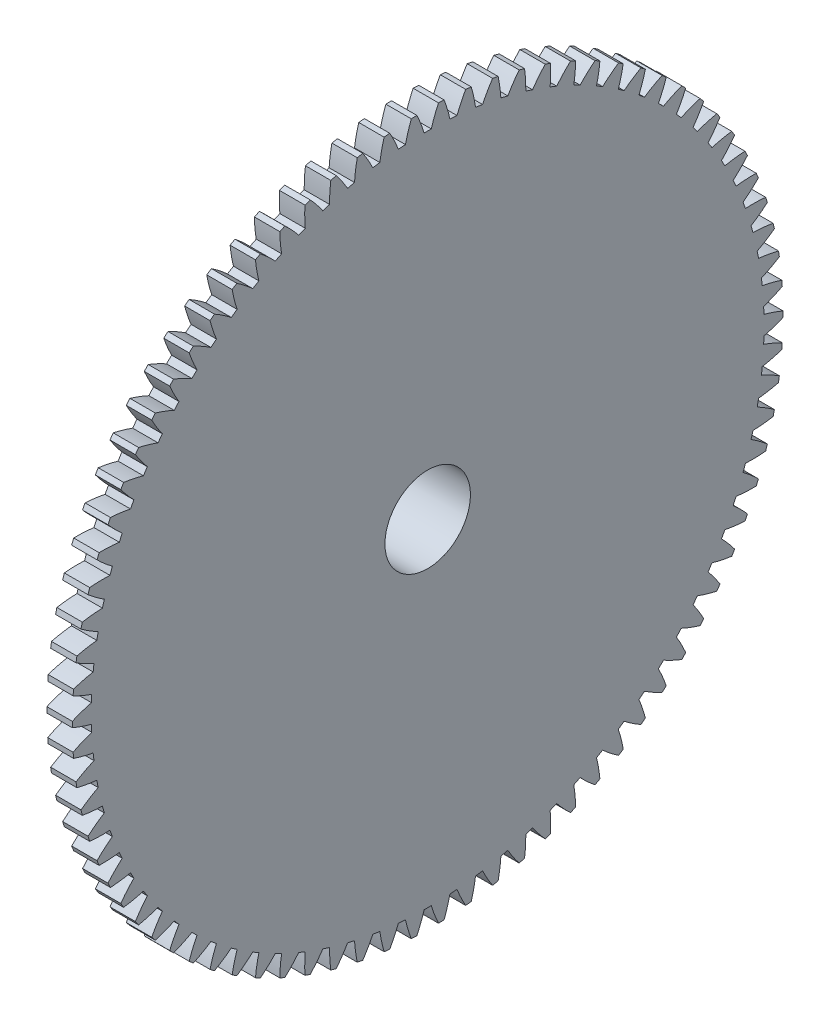
SolidWorks part; units mm, degrees
ref_plane "Plane1" through (0, 0, 0) normal (0, 0, 1) x (1, 0, 0)
ref_plane "Plane2" through (0, 0, 0) normal (0, 1, 0) x (1, 0, 0)
ref_plane "Plane3" through (0, 0, 0) normal (1, 0, 0) x (0, 0, -1)
sketch "HoldingSke" plane through (0, 0, 0) normal (0, 1, 0) x (1, 0, 0)
  line L0 (0, 0) -> (0.1392, -0.9903)
  line L1 (-15, 0) -> (100, 0) construction
  line L2 (0, 0) -> (-2.1039, 2.3779)
  line L3 (0, 0) -> (-11.863, 4.5341)
  line L4 (0, 0) -> (1.2019, 8.552)
  line L5 (0, 0) -> (-46.8476, -17.4728)
  line L6 (0, 0) -> (-2.4869, -1.6779)
  line L7 (-2.1039, 2.3779) -> (8.6586, 51.2059)
  line L8 (-76.2, 54.61) -> (-75.2, 54.61)
  line L9 (-71.009, 38.7566) -> (-53.1078, 45.2721)
  line L10 (-76.2, 71.12) -> (104.1128, 71.12)
  line L11 (0, 0) -> (-3, 0)
  line L12 (-76.2, 101.6) -> (-76.162, 101.6)
  line L13 (24.9733, 27.94) -> (52.9518, 28.4284)
  line L14 (24.9733, 27.94) -> (24.9743, 27.94)
  line L15 (24.9733, 27.94) -> (100.4006, 29.5858)
  line L16 (-63.627, -1) -> (-12.827, -1)
  circle A0 centre (0, 0) radius 3
  circle A1 centre (0, 0) radius 37.5
  circle A2 centre (0, 0) radius 37.5
  circle A3 centre (0, 0) radius 3
  dimension "MHD" = 75
  dimension "Hub_dia" = 75
  dimension "Bore" = 6
  dimension "MBD" = 6
  dimension "Num_teeth" = 82
  dimension "Pitch" = 1
  dimension "Overall_len" = 50
  dimension "Show_teeth" = 82
  dimension "Thickness" = 3
  dimension "OAL" = 50.0001
  dimension "T_dim" = 1
  dimension "Ap" = 20
  dimension "H" = 19.05
  dimension "Pitch_radius" = 180.3128
  dimension "Width" = 3
  dimension "Backlash" = 0.038
  dimension "Addendum_fac" = 1
  dimension "Dedendum_fac" = 1.25
  dimension "Clearance_fac" = 0.25
  dimension "Dedendum_add" = 0.001
  dimension "Module" = 1
sketch "BasProSke" plane through (0, 0, 0) normal (0, 1, 0) x (1, 0, 0)
  line L0 (-10, 0) -> (60, 0) construction
  line L1 (0, 0) -> (0, 42)
  line L2 (0, 0) -> (3, 0)
  line L3 (3, 0) -> (3, 42)
  line L4 (3, 42) -> (0, 42)
  dimension "Thickness" = 3
  dimension "Diameter" = 84
revolve "Base-Revolve" add sketch "BasProSke" angle 360 about L0
sketch "TooCutSke" plane through (0, 0, 0) normal (1, 0, 0) x (0, 0, -1)
  line L1 (0, 0) -> (0, 107) construction
  line L2 (0, 0) -> (-0.8518, 40.9911) construction
  line L3 (0, 0) -> (-3.1403, 81.9272) construction
  line L4 (-0.8518, 40.9911) -> (-1.5702, 40.9636) construction
  arc A0 (0.4198, 39.7468) -> (-0.4198, 39.7468) centre (0, 0) ccw
  arc A1 (1.2904, 42.0056) -> (-1.2904, 42.0056) centre (0, 0) ccw
  circle A2 centre (0, 0) radius 41 construction
  circle A3 centre (0, 0) radius 38.5274 construction
  arc A4 (-0.4198, 39.7468) -> (-1.2904, 42.0056) centre (-16.1163, 34.9947) ccw
  arc A5 (1.2904, 42.0056) -> (0.4198, 39.7468) centre (16.1163, 34.9947) ccw
  dimension "Root_dia" = 79.498
  dimension "Overcut_dia" = 84.0508
  dimension "Pitch_dia" = 82
  dimension "Base_dia" = 77.0548
  dimension "Flank_rad" = 16.4
  dimension "Half_ang" = 2.195
  dimension "Half_CT" = 0.7189
extrude "ToothCut" cut sketch "TooCutSke" along normal through all
fillet "Breaks" [suppressed] radius 0.02 tangent propagation no
fillet "RootFillets" [suppressed] radius 0.251
pattern_circular "TeethCuts" count 82 over 360 about axis through (-10, 0, 0) along (1, 0, 0) of "ToothCut", "RootFillets", "Breaks"
sketch "HubNeaOneSke" plane through (0, 0, 0) normal (-1, 0, 0) x (0, 0, 1)
  circle A0 centre (0, 0) radius 37.5
  dimension "Diameter" = 75
extrude "HubNearOne" [suppressed] add sketch "HubNeaOneSke" along normal blind 47.0001
sketch "HubNeaBotSke" plane through (0, 0, 0) normal (-1, 0, 0) x (0, 0, 1)
  circle A0 centre (0, 0) radius 37.5
  dimension "Diameter" = 75
extrude "HubNearBoth" [suppressed] add sketch "HubNeaBotSke" along normal blind 23.5
ref_plane "FarPln" through (3, 0, 0) normal (1, 0, 0) x (0, 0, -1)
sketch "HubFarSke" plane through (3, 0, 0) normal (1, 0, 0) x (0, 0, -1)
  circle A0 centre (0, 0) radius 37.5
  dimension "Diameter" = 75
extrude "HubFar" [suppressed] add sketch "HubFarSke" along normal blind 23.5
sketch "BorSke" plane through (0, 0, 0) normal (1, 0, 0) x (0, 0, -1)
  circle A0 centre (0, 0) radius 3
  dimension "Diameter" = 6
extrude "Bore" cut sketch "BorSke" along normal mid plane 100.0001
sketch "KeySke" plane through (0, 0, 0) normal (1, 0, 0) x (0, 0, -1)
  line L0 (-1, 0) -> (-1, 4)
  line L1 (-1, 4) -> (1, 4)
  line L2 (1, 4) -> (1, 0)
  line L3 (0, 0) -> (0, 34) construction
  line L4 (-1, 0) -> (1, 0)
  dimension "Offset" = 4
  dimension "Width" = 2
extrude "Keyway" [suppressed] cut sketch "KeySke" along normal mid plane 100.0001
pattern_circular "Keyway2" [suppressed] count 2 every 90 about axis through (-10, 0, 0) along (1, 0, 0) reverse direction yes
sketch "Sketch1" plane through (3, 0, 0) normal (1, 0, 0) x (0, 0, -1)
  circle A0 centre (0, 0) radius 3 construction
  circle A1 centre (0, 0) radius 3
extrude "Boss-Extrude1" add sketch "Sketch1" against normal up to surface (3 mm away) up to face at (0, 0, -3)
sketch "Sketch2" plane through (3, 0, 0) normal (1, 0, 0) x (0, 0, -1)
  line L0 (-1.8, 2.0125) -> (-1.8, -2.0125)
  line L1 (1.8, 2.0125) -> (1.8, -2.0125)
  line L2 (-1.8, 0) -> (1.8, 0) construction
  circle A0 centre (0, 0) radius 2.7
  point P9 (0, 0)
  dimension "D1" = 5.4
  dimension "D2" = 3.6
extrude "Cut-Extrude1" cut sketch "Sketch2" against normal up to surface (3 mm away) contours L0 L2 L1 A0 | L2 L0 A0 L1 region at (3, 1.25, 0) region at (3, -1.25, 0) up to face at (0, 0, 0)
sketch "Sketch3" plane through (3, 0, 0) normal (1, 0, 0) x (0, 0, -1)
  circle A0 centre (0, 0) radius 3
  dimension "D1" = 6
extrude "Cut-Extrude2" cut sketch "Sketch3" against normal up to surface (3 mm away) up to face at (0, 0, 0)
sketch "Sketch4" plane through (0, 0, 0) normal (-1, 0, 0) x (0, 0, 1)
  circle A0 centre (0, 0) radius 5.05
  dimension "D1" = 10.1
extrude "Cut-Extrude3" cut sketch "Sketch4" against normal through all
sketch "Sketch5" plane through (0, 0, 0) normal (-1, 0, 0) x (0, 0, 1)
  line L1 (6.2989, -3.5812) -> (6.2508, 3.6644)
  line L2 (6.2508, 3.6644) -> (-0.048, 7.2456)
  line L3 (-0.048, 7.2456) -> (-6.2989, 3.5812)
  line L4 (-6.2989, 3.5812) -> (-6.2508, -3.6644)
  line L5 (-6.2508, -3.6644) -> (0.048, -7.2456)
  line L6 (0.048, -7.2456) -> (6.2989, -3.5812)
  circle A0 centre (0, 0) radius 5.05 construction
  circle A1 centre (0, 0) radius 5.05
  circle A2 centre (0, 0) radius 6.275 construction
  dimension "D1" = 12.55
extrude "Boss-Extrude2" add sketch "Sketch5" along normal blind 12.85
sketch "Sketch6" plane through (0, 0, 0) normal (-1, 0, 0) x (0, 0, 1)
  line L12 (0.0557, -8.4003) -> (7.3027, -4.1519)
  line L13 (7.3027, -4.1519) -> (7.247, 4.2484)
  line L14 (7.247, 4.2484) -> (-0.0557, 8.4003)
  line L15 (-0.0557, 8.4003) -> (-7.3027, 4.1519)
  line L16 (-7.3027, 4.1519) -> (-7.247, -4.2484)
  line L17 (-7.247, -4.2484) -> (0.0557, -8.4003)
  line L18 (0.0557, -8.4003) -> (7.3027, -4.1519)
  line L19 (7.3027, -4.1519) -> (7.247, 4.2484)
  line L20 (7.247, 4.2484) -> (-0.0557, 8.4003)
  line L21 (-0.0557, 8.4003) -> (-7.3027, 4.1519)
  line L22 (-7.3027, 4.1519) -> (-7.247, -4.2484)
  line L23 (-7.247, -4.2484) -> (0.0557, -8.4003)
  dimension "D1" = 1
extrude "Boss-Extrude3" add sketch "Sketch6" along normal blind 5.05
sketch "Sketch7" plane through (-12.85, 0, 0) normal (-1, 0, 0) x (0, 0, 1)
  circle A0 centre (0, 0) radius 5.05 construction
  circle A1 centre (0, 0) radius 5.05
extrude "Cut-Extrude4" cut sketch "Sketch7" against normal up to surface (15.85 mm away) up to face at (3, 0, 5.05)
equation "' \"Module@HoldingSke\" = 6.35"
equation "' \"Num_teeth@HoldingSke\" = 12"
equation "' \"Ap@HoldingSke\" =  20"
equation "' \"Ap@HoldingSke\" = 20"
equation "' \"Width@HoldingSke\" = 0.5 * 25.4"
equation "' \"Hub_dia@HoldingSke\"= 1 * 25.4"
equation "' \"Hub_dia@HoldingSke\" = 1 * 25.4"
equation "' \"Overall_len@HoldingSke\" = 1.0 * 25.4"
equation "' \"Bore@HoldingSke\" = 0.75 * 25.4"
equation "' \"T_dim@HoldingSke\" = 0.1 * 25.4"
equation "' \"Width@KeySke\" = 0.25 * 25.4"
equation "' \"Show_teeth@HoldingSke\" = 13"
equation "' \"Backlash@HoldingSke\" = 0.009 * 25.4"
equation "' \"Addendum_fac@HoldingSke\" = 1.0"
equation "' \"Dedendum_fac@HoldingSke\" = 1.25"
equation "' \"Dedendum_add@HoldingSke\" = 0.00005 * 25.4"
equation "' \"Clearance_fac@HoldingSke\" = 0.25"
equation "\"Pitch@HoldingSke\" = 1 / \"Module@HoldingSke\""
equation "\"Overcut_dia@TooCutSke\" = (\"Num_teeth@HoldingSke\" + 2 * \"Addendum_fac@HoldingSke\") / \"Pitch@HoldingSke\" + 0.002 * 25.4"
equation "\"Pitch_dia@TooCutSke\" = \"Num_teeth@HoldingSke\" / \"Pitch@HoldingSke\""
equation "\"Base_dia@TooCutSke\" = \"Num_teeth@HoldingSke\" / \"Pitch@HoldingSke\" * cos((\"Ap@HoldingSke\"  * 3.14159265 / 180))"
equation "\"Root_dia@TooCutSke\" = (\"Num_teeth@HoldingSke\" + 2) / \"Pitch@HoldingSke\" - 2 * (\"Addendum_fac@HoldingSke\" + \"Dedendum_fac@HoldingSke\") / \"Pitch@HoldingSke\" - \"Dedendum_add@HoldingSke\" * 2"
equation "\"Half_ang@TooCutSke\" = 180 / \"Num_teeth@HoldingSke\""
equation "\"Half_CT@TooCutSke\" = \"Num_teeth@HoldingSke\" / \"Pitch@HoldingSke\" * sin((3.14159265 / 2 / \"Num_teeth@HoldingSke\")) / 2 - 7 * \"Backlash@HoldingSke\" / 4"
equation "\"Flank_rad@TooCutSke\" = \"Num_teeth@HoldingSke\" / \"Pitch@HoldingSke\" / 5"
equation "\"Radius@RootFillets\" = \"Clearance_fac@HoldingSke\" / \"Pitch@HoldingSke\" + \"Dedendum_add@HoldingSke\""
equation "\"Break_rad@Breaks\" = 0.02 / \"Pitch@HoldingSke\""
equation "\"Thickness@HoldingSke\" = \"Width@HoldingSke\""
equation "\"OAL@HoldingSke\" = \"Thickness@HoldingSke\""
equation "\"MHD@HoldingSke\" = (\"Num_teeth@HoldingSke\" + 2) / \"Pitch@HoldingSke\" - 2 * (\"Addendum_fac@HoldingSke\" + \"Dedendum_fac@HoldingSke\")  / \"Pitch@HoldingSke\" - \"Dedendum_add@HoldingSke\" * 2"
equation "\"MBD@HoldingSke\" = (\"Num_teeth@HoldingSke\" + 2) / \"Pitch@HoldingSke\" - 2 * (\"Addendum_fac@HoldingSke\" + \"Dedendum_fac@HoldingSke\")  / \"Pitch@HoldingSke\" - \"Dedendum_add@HoldingSke\" * 2 - 0.002 * 25.4"
equation "\"MHD@HoldingSke\" = ((sgn( \"MHD@HoldingSke\" - \"Hub_dia@HoldingSke\" )-1)*( \"MHD@HoldingSke\" - \"Hub_dia@HoldingSke\" ))/-2+ \"Hub_dia@HoldingSke\""
equation "\"MBD@HoldingSke\" = ((sgn( \"MBD@HoldingSke\" - \"Bore@HoldingSke\" )-1)*( \"MBD@HoldingSke\" - \"Bore@HoldingSke\" ))/-2+ \"Bore@HoldingSke\""
equation "\"OAL@HoldingSke\" = ((sgn( \"OAL@HoldingSke\" - \"Overall_len@HoldingSke\" )+1)*( \"OAL@HoldingSke\" - \"Overall_len@HoldingSke\" ))/2 + \"Overall_len@HoldingSke\" + 0.000002 * 25.4"
equation "\"Num_teeth@TeethCuts\" = int( \"Show_teeth@HoldingSke\" ) + 1"
equation "\"Num_teeth@TeethCuts\" = ((sgn( \"Num_teeth@TeethCuts\" - \"Num_teeth@HoldingSke\" )-1)*( \"Num_teeth@TeethCuts\" - \"Num_teeth@HoldingSke\" ))/-2+ \"Num_teeth@HoldingSke\""
equation "\"Num_teeth@TeethCuts\" = ((sgn( \"Num_teeth@TeethCuts\" - 2.0)+1)*( \"Num_teeth@TeethCuts\" - 2.0))/2 +2.0"
equation "\"Angle@TeethCuts\" = 360.0 / \"Num_teeth@HoldingSke\""
equation "\"Diameter@BasProSke\" = (\"Num_teeth@HoldingSke\" + 2 * \"Addendum_fac@HoldingSke\") / \"Pitch@HoldingSke\""
equation "\"Thickness@BasProSke\"  = \"Thickness@HoldingSke\""
equation "' \"Fillet_rad@BasProSke\" =  \"Thickness@HoldingSke\" * 0.05"
equation "' \"Fillet_rad@BasProSke\" = \"Thickness@HoldingSke\" * 0.05"
equation "\"MHD@HoldingSke\" = ((sgn( \"MHD@HoldingSke\" - \"Root_dia@TooCutSke\" )-1)*( \"MHD@HoldingSke\" - \"Root_dia@TooCutSke\" ))/-2+ \"Root_dia@TooCutSke\""
equation "\"Diameter@HubNeaOneSke\" = \"MHD@HoldingSke\""
equation "\"Length@HubNearOne\" = \"OAL@HoldingSke\" - \"Thickness@BasProSke\""
equation "\"Diameter@HubNeaBotSke\" = \"MHD@HoldingSke\""
equation "\"Length@HubNearBoth\" = ( \"OAL@HoldingSke\" - \"Thickness@BasProSke\" ) / 2.0"
equation "\"Thickness@FarPln\" = \"Thickness@BasProSke\""
equation "\"Diameter@HubFarSke\" = \"MHD@HoldingSke\""
equation "\"Length@HubFar\" = ( \"OAL@HoldingSke\" - \"Thickness@BasProSke\" ) / 2.0"
equation "\"Diameter@BorSke\" = \"MBD@HoldingSke\""
equation "\"D1@Bore\" = \"OAL@HoldingSke\" * 2.0"
equation "\"D1@Keyway\" = \"OAL@HoldingSke\" * 2.0"
equation "\"Offset@KeySke\" = \"T_dim@HoldingSke\" + \"MBD@HoldingSke\" / 2.0"
